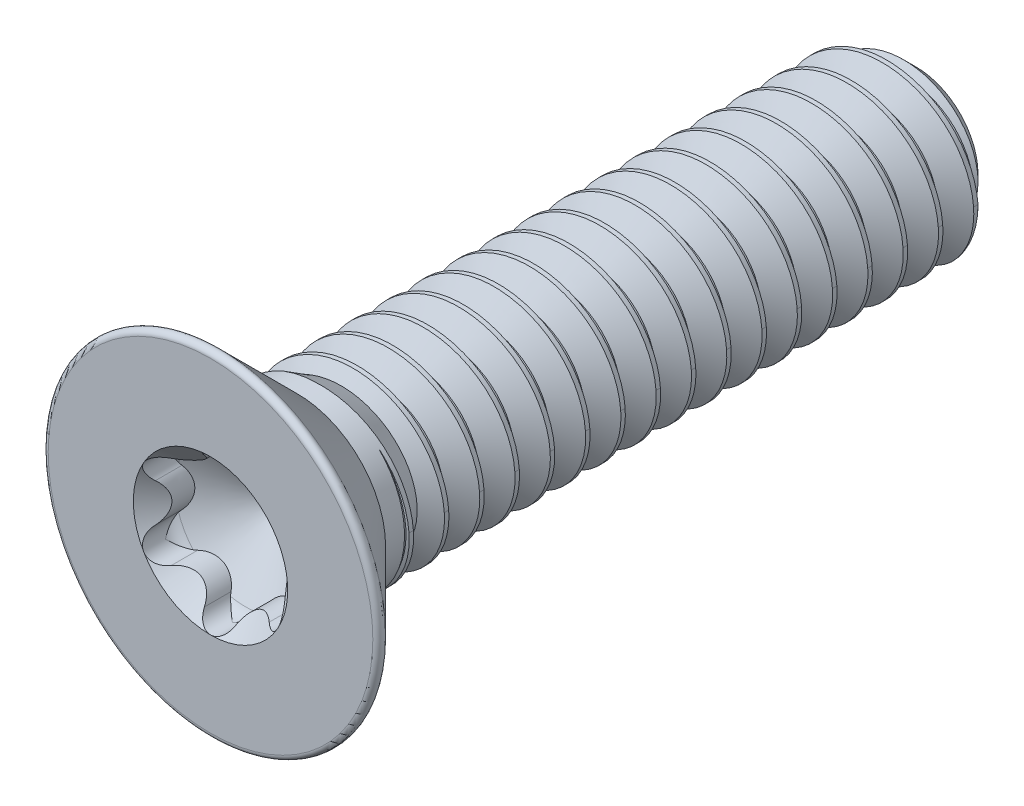
SolidWorks part; units mm, degrees
ref_plane "Front Plane" through (0, 0, 0) normal (0, 0, 1) x (1, 0, 0)
ref_plane "Top Plane" through (0, 0, 0) normal (0, 1, 0) x (1, 0, 0)
ref_plane "Right Plane" through (0, 0, 0) normal (1, 0, 0) x (0, 0, -1)
sketch "Sketch1" plane through (0, 0, 0) normal (1, 0, 0) x (0, 0, -1)
  line L0 (0, 0) -> (8, 0) construction
  line L1 (0, -1.9) -> (0, 1.9) construction
  line L2 (8, 1) -> (8, -1) construction
  line L3 (1.2, 0.7849) -> (1.2, -0.7849) construction
  line L5 (0.1024, 1.8824) -> (1.2, 0.7849) construction
  line L6 (8, 1) -> (0.9849, 1) construction
  line L7 (7.975, 1.0433) -> (8.175, 0.6969) construction
  line L8 (8.175, 0.6969) -> (8.375, 1.0433) construction
  line L9 (8.375, 1.0433) -> (7.975, 1.0433) construction
  line L10 (8, -1) -> (0.9849, -1) construction
  line L11 (8.175, 0.7402) -> (8.175, 0.6969) construction
  line L12 (8.175, 1.0433) -> (8.175, 1) construction
  line L13 (8.35, 1) -> (8, 1) construction
  line L14 (8.15, 0.7402) -> (8.2, 0.7402) construction
  line L15 (8.175, 1.0217) -> (7.9875, 1.0217) construction
  line L16 (8.175, 1.0217) -> (8.3625, 1.0217) construction
  line L17 (1.2, 0.7849) -> (8, 0.7849) construction
  line L18 (0.1024, -1.8824) -> (1.2, -0.7849) construction
  line L19 (0, -1.9) -> (1.2, -1.9) construction
  line L20 (1.2, -1.9) -> (1.2, 1.9) construction
  line L21 (1.2, 1.9) -> (0, 1.9) construction
  arc A0 (0, 1.84) -> (0.1024, 1.8824) centre (0.06, 1.84) cw
  arc A1 (0, -1.84) -> (0.1024, -1.8824) centre (0.06, -1.84) ccw
  point P7 (1.2, 0)
  point P17 (1.2, 0.7849)
  point P18 (0, 1.9)
  point P29 (7, -1)
  dimension "D3" = 0.06
  dimension "Length" = 8
  dimension "Thread Size" = 2
  dimension "Head Diameter" = 3.8
  dimension "Head Height" = 1.2
  dimension "Thread Pitch" = 0.4
  dimension "D2" = 0.05
  dimension "D1" = 1
  dimension "Countersink Angle" = 90
sketch "Sketch2" plane through (0, 0, 0) normal (0, 0, 1) x (1, 0, 0)
  line L0 (0, -1.9) -> (0, 1.9) construction
  circle A0 centre (0, 0) radius 1
  circle A1 centre (0, 0) radius 1.9 construction
  circle A2 centre (0, 0) radius 0.875 construction
  point P8 (0, -0.875)
  dimension "D1" = 1.75
extrude "Boss-Extrude1" add sketch "Sketch2" against normal up to vertex (8 mm away) up to point (0, 0, -8)
chamfer "Chamfer1" distance 0.3 angle 45 1 edges at (1, 0, -8)
sketch "Sketch3" plane through (0, 0, 0) normal (1, 0, 0) x (0, 0, -1)
  line L0 (0.1024, 1.8824) -> (1.2, 0.7849) construction
  line L1 (0.1024, 1.8824) -> (1.2, 0.7849)
  line L2 (1.2, 0.7849) -> (1.2, 0)
  line L3 (1.2, 0.7849) -> (1.2, -0.7849) construction
  line L4 (1.2, 0) -> (0, 0)
  line L5 (0, 1.84) -> (0, 0)
  arc A0 (0.1024, 1.8824) -> (0, 1.84) centre (0.06, 1.84) ccw construction
  arc A1 (0.1024, 1.8824) -> (0, 1.84) centre (0.06, 1.84) ccw
revolve "Revolve1" add sketch "Sketch3" angle 360 about L4
sketch "Sketch4" plane through (0, 0, 0) normal (1, 0, 0) x (0, 0, -1)
  line L0 (1.2, 0.7849) -> (1.9849, 0)
  line L1 (0, 0) -> (8, 0) construction
  line L2 (1.9849, 0) -> (1.2, 0)
  line L6 (1.2, 0) -> (1.2, 0.7849)
revolve "Revolve2" add sketch "Sketch4" angle 360 about L2
ref_plane "Plane1" through (0, 0, 20.448) normal (0, 0, -1) x (-1, 0, 0)
sketch "Sketch5" plane through (0, 0, 0) normal (0, 0, 1) x (1, 0, 0)
  line L0 (0, 0.875) -> (0, 0) construction
  line L1 (0, 0) -> (-0.875, 0) construction
  line L2 (-0.7578, 0.4375) -> (0, 0) construction
  line L3 (0, 0) -> (-0.8525, -0.4922) construction
  line L4 (-0.7578, 0.4375) -> (-0.8525, 0.4922)
  line L5 (-0.8525, -0.4922) -> (-0.6631, -0.3828) construction
  line L6 (-0.7578, -0.4375) -> (-0.8525, -0.4922)
  line L7 (-0.6631, -0.3828) -> (-0.7578, -0.4375) construction
  circle A0 centre (0, 0) radius 0.875 construction
  circle A1 centre (0, 0) radius 0.875 construction
  circle A2 centre (0, 0) radius 0.7656 construction
  circle A3 centre (0, 0) radius 0.6563 construction
  arc A4 (-0.8525, 0.4922) -> (-0.8525, -0.4922) centre (0, 0) ccw
  arc A5 (-0.734, 0.2177) -> (-0.7578, 0.4375) centre (-0.5956, 0.3439) cw
  arc A6 (-0.734, -0.2177) -> (-0.7578, -0.4375) centre (-0.5956, -0.3439) ccw
  ellipse E1 centre (-0.875, 0) end of major axis (-0.875, -0.2848) minor radius 0.2187 (-0.734, -0.2177) -> (-0.734, 0.2177) ccw
  dimension "D2" = 1.5312
  dimension "D3" = 1.3125
  dimension "D1" = 30
sketch "Sketch6" plane through (0, 0, 0) normal (1, 0, 0) x (0, 0, -1)
  line L0 (0, 0.875) -> (0.2474, 0.875)
  line L2 (0, 0) -> (0.81, 0)
  line L3 (0, 0.7656) -> (0, -0.7656) construction
  line L4 (0.81, 0) -> (0.81, -1.1749) construction
  line L6 (0, 0.875) -> (0, 0)
  line L7 (0.1024, -1.8824) -> (1.2, -0.7849) construction
  line L8 (0.81, 0) -> (0.81, 0.1215)
  line L9 (0.3931, 0.7939) -> (0.81, 0.1215)
  arc A2 (0.2474, 0.875) -> (0.3931, 0.7939) centre (0.2474, 0.7036) cw
  point P9 (0.3429, 0.875)
  dimension "D4" = 0.1714
  dimension "D1" = 0.3429
  dimension "D2" = 0.81
  dimension "D3" = 0.1215
revolve "Cut-Revolve1" cut sketch "Sketch6" angle 360 about L2
extrude "Boss-Extrude2" add sketch "Sketch5" against normal up to next contours E1 A5 L4 A4 L6 A6
pattern_circular "CirPattern1" count 6 over 360 about axis through (0, 0, 0) along (0, 0, -1) of "Boss-Extrude2"
sketch "Sketch7" plane through (0, 0, 0) normal (0, 0, 1) x (1, 0, 0)
  circle A0 centre (0, 0) radius 0.875 construction
  circle A1 centre (0, 0) radius 0.875
extrude "Cut-Extrude1" cut sketch "Sketch7" against normal up to next (0.81 mm away) draft 45
ref_plane "Plane2" through (0, 0, -1.2) normal (0, 0, -1) x (-1, 0, 0)
split "Split1" trim tools "Plane2" bodies to split 109 resulting bodies 125 126
sketch "Sketch8" plane through (0, 0, 0) normal (1, 0, 0) x (0, 0, -1)
  line L0 (7.9875, 1.0217) -> (8.3625, 1.0217)
  line L1 (8.3625, 1.0217) -> (8.2, 0.7402)
  line L2 (8.2, 0.7402) -> (8.15, 0.7402)
  line L3 (8.15, 0.7402) -> (7.9875, 1.0217)
sketch "Sketch9" plane through (0, 0, -8) normal (0, 0, -1) x (-1, 0, 0)
  circle A0 centre (0, 0) radius 1 construction
  circle A1 centre (0, 0) radius 1
curve "Helix/Spiral1" pitch 0.4 height 8 radius 1 centre (0, 0, -8) axis (0, 0, 1) start towards (0, 1, 0)
sweep "Cut-Sweep1" cut profiles "Sketch8" path "Helix/Spiral1" align with end faces yes
sketch "Sketch10" plane through (0, 0, -1.2) normal (0, 0, -1) x (-1, 0, 0)
  circle A0 centre (0, 0) radius 1 construction
  circle A4 centre (0, 0) radius 1
extrude "Boss-Extrude3" add sketch "Sketch10" along normal up to next (6.8 mm away) draft 30
sketch "Sketch11" plane through (0, 0, 0) normal (1, 0, 0) x (0, 0, -1)
  point P0 (0, -0.875)
ref_axis "Axis1" through (0, 0, -8.5591) along (0, 0, 1)
equation "\"D4@Helix/Spiral1\" = \"Thread Pitch@Sketch1\""
equation "\"D3@Helix/Spiral1\"=\"Length@Sketch1\""
equation "\"D2@Sketch5\" = \"D1@Sketch2\" * 0.875"
equation "\"D3@Sketch5\" = \"D1@Sketch2\" * 0.75"
equation "\"D1@Chamfer1\"=\"D4@Helix/Spiral1\"*.75"
equation "\"D2@Sketch1\" = \"Thread Pitch@Sketch1\" / 8"
equation "\"D1@Sketch1\" = \"Thread Pitch@Sketch1\" * 2.5"
equation "\"D1@Sketch6\" = \"Head Height@Sketch1\" / 3.5"
equation "\"D2@Sketch6\" = \"Head Height@Sketch1\" * .675"
equation "\"D3@Sketch1\"=\"Head Height@Sketch1\"*.05"
equation "\"D3@Sketch6\" = \"D2@Sketch6\" * .15"
equation "\"D4@Sketch6\" = \"D1@Sketch6\" * .5"
